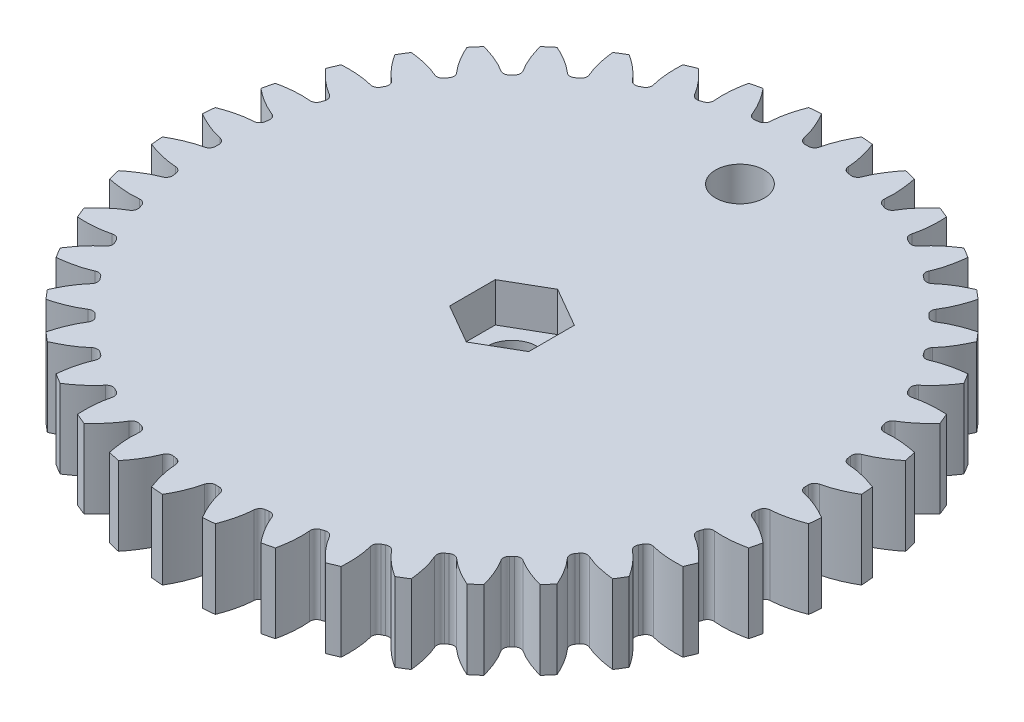
SolidWorks part; units mm, degrees
ref_plane "Front Plane" through (0, 0, 0) normal (0, 0, 1) x (1, 0, 0)
ref_plane "Top Plane" through (0, 0, 0) normal (0, 1, 0) x (1, 0, 0)
ref_plane "Right Plane" through (0, 0, 0) normal (1, 0, 0) x (0, 0, -1)
sketch "Sketch2" plane through (0, 0, 0) normal (0, 1, 0) x (1, 0, 0)
  circle A0 centre (0, 0) radius 53.34
  dimension "D1" = 106.68
extrude "Boss-Extrude1" add sketch "Sketch2" along normal blind 12.7
sketch "Sketch3" plane through (0, 0, 0) normal (0, -1, 0) x (-1, 0, 0)
  line L0 (0, 0) -> (47.7222, -1.163) construction
  line L1 (0, 0) -> (47.7222, 1.163) construction
  line L2 (47.7222, -1.163) -> (47.6109, -1.1603)
  line L3 (47.7222, 1.163) -> (47.6109, 1.1603)
  circle A0 centre (0, 0) radius 53.34
  circle A1 centre (0, 0) radius 50.8
  circle A2 centre (0, 0) radius 47.752
  circle A3 centre (0, 0) radius 47.625
  spline S0 degree 4 poles (47.7222, 1.163) (47.731, 1.1633) (47.7556, 1.1645) (47.802, 1.1678) (47.8777, 1.1747) (47.9741, 1.186) (48.0986, 1.2033) (48.2451, 1.2271) (48.4058, 1.257) (48.5805, 1.2934) (48.7546, 1.3332) (48.928, 1.3762) (49.1005, 1.4219) (49.3093, 1.4808) (49.5592, 1.5562) (49.8507, 1.6513) (50.1805, 1.7675) (50.5158, 1.8948) (50.845, 2.0273) (51.1768, 2.1695) (51.4972, 2.313) (51.8289, 2.4707) (52.1347, 2.6205) (52.4761, 2.7979) (52.7513, 2.9438) (53.113, 3.1463) (53.3263, 3.2689) (53.5754, 3.4159) (53.6857, 3.483) (53.7537, 3.5243) knots 0 0 0 0 0 0.005377 0.015084 0.028532 0.04661 0.064855 0.092111 0.119476 0.146842 0.174209 0.201575 0.228941 0.256307 0.307035 0.361767 0.4165 0.471232 0.525964 0.580697 0.635429 0.690161 0.744894 0.799626 0.854358 0.909091 0.954545 1 1 1 1 1 construction
  spline S1 degree 4 poles (47.7222, 1.163) (47.731, 1.1633) (47.7556, 1.1645) (47.802, 1.1678) (47.8777, 1.1747) (47.9741, 1.186) (48.0986, 1.2033) (48.2451, 1.2271) (48.4058, 1.257) (48.5805, 1.2934) (48.7546, 1.3332) (48.928, 1.3762) (49.1005, 1.4219) (49.3093, 1.4808) (49.5592, 1.5562) (49.8507, 1.6513) (50.1805, 1.7675) (50.5158, 1.8948) (50.845, 2.0273) (51.1768, 2.1695) (51.4972, 2.313) (51.8289, 2.4707) (52.1347, 2.6205) (52.4761, 2.7979) (52.7513, 2.9438) (53.0346, 3.1024) (53.1723, 3.1808) (53.2426, 3.2213) knots 0 0 0 0 0 0.005377 0.015084 0.028532 0.04661 0.064855 0.092111 0.119476 0.146842 0.174209 0.201575 0.228941 0.256307 0.307035 0.361767 0.4165 0.471232 0.525964 0.580697 0.635429 0.690161 0.744894 0.799626 0.854358 0.909091 0.909091 0.909091 0.909091 0.909091
  spline S2 degree 4 poles (47.7222, -1.163) (47.731, -1.1633) (47.7556, -1.1645) (47.802, -1.1678) (47.8777, -1.1747) (47.9741, -1.186) (48.0986, -1.2033) (48.2451, -1.2271) (48.4058, -1.257) (48.5805, -1.2934) (48.7546, -1.3332) (48.928, -1.3762) (49.1005, -1.4219) (49.3093, -1.4808) (49.5592, -1.5562) (49.8507, -1.6513) (50.1805, -1.7675) (50.5158, -1.8948) (50.845, -2.0273) (51.1768, -2.1695) (51.4972, -2.313) (51.8289, -2.4707) (52.1347, -2.6205) (52.4761, -2.7979) (52.7513, -2.9438) (53.113, -3.1463) (53.3263, -3.2689) (53.5754, -3.4159) (53.6857, -3.483) (53.7537, -3.5243) knots 0 0 0 0 0 0.005377 0.015084 0.028532 0.04661 0.064855 0.092111 0.119476 0.146842 0.174209 0.201575 0.228941 0.256307 0.307035 0.361767 0.4165 0.471232 0.525964 0.580697 0.635429 0.690161 0.744894 0.799626 0.854358 0.909091 0.954545 1 1 1 1 1 construction
  spline S3 degree 4 poles (47.7222, -1.163) (47.731, -1.1633) (47.7556, -1.1645) (47.802, -1.1678) (47.8777, -1.1747) (47.9741, -1.186) (48.0986, -1.2033) (48.2451, -1.2271) (48.4058, -1.257) (48.5805, -1.2934) (48.7546, -1.3332) (48.928, -1.3762) (49.1005, -1.4219) (49.3093, -1.4808) (49.5592, -1.5562) (49.8507, -1.6513) (50.1805, -1.7675) (50.5158, -1.8948) (50.845, -2.0273) (51.1768, -2.1695) (51.4972, -2.313) (51.8289, -2.4707) (52.1347, -2.6205) (52.4761, -2.7979) (52.7513, -2.9438) (53.0346, -3.1024) (53.1723, -3.1808) (53.2426, -3.2213) knots 0 0 0 0 0 0.005377 0.015084 0.028532 0.04661 0.064855 0.092111 0.119476 0.146842 0.174209 0.201575 0.228941 0.256307 0.307035 0.361767 0.4165 0.471232 0.525964 0.580697 0.635429 0.690161 0.744894 0.799626 0.854358 0.909091 0.909091 0.909091 0.909091 0.909091
  dimension "D1" = 106.68
  dimension "D2" = 101.6
  dimension "D3" = 95.504
  dimension "D4" = 95.25
extrude "Cut-Extrude1" cut sketch "Sketch3" against normal blind 12.7 contours A1 S3 A0 S1 | A2 S3 A1 S1 | L2 S3 A2 S1 L3 A3 region at (-47.6838, 0, 0) region at (-49.4115, 0, 0) region at (-52.1487, 0, 0)
fillet "Fillet2" radius 1.016 2 edges at (-47.6109, 6.35, -1.1603) (-47.6109, 6.35, 1.1603)
pattern_circular "CirPattern1" count 40 over 360 about axis through (0, 12.7, 0) along (0, 1, 0) of "Fillet2", "Cut-Extrude1"
sketch "Sketch4" plane through (0, 12.7, 0) normal (0, 1, 0) x (1, 0, 0)
  circle A0 centre (0, 0) radius 4.0957
  dimension "D1" = 8.1915
extrude "Cut-Extrude2" cut sketch "Sketch4" against normal through all
sketch "Sketch5" plane through (0, 12.7, 0) normal (0, 1, 0) x (1, 0, 0)
  line L1 (0, 7.3763) -> (-6.3881, 3.6882)
  line L2 (-6.3881, 3.6882) -> (-6.3881, -3.6882)
  line L3 (-6.3881, -3.6882) -> (0, -7.3763)
  line L4 (0, -7.3763) -> (6.3881, -3.6882)
  line L5 (6.3881, -3.6882) -> (6.3881, 3.6882)
  line L6 (6.3881, 3.6882) -> (0, 7.3763)
  circle A0 centre (0, 0) radius 6.3881 construction
  dimension "D1" = 12.7762
extrude "Cut-Extrude3" cut sketch "Sketch5" against normal blind 6.35
sketch "Sketch6" plane through (0, 12.7, 0) normal (0, 1, 0) x (1, 0, 0)
  line L0 (0, 0) -> (0, 36.83) construction
  circle A0 centre (0, 36.83) radius 3.937
  dimension "D2" = 7.874
  dimension "D1" = 36.83
extrude "Cut-Extrude4" cut sketch "Sketch6" against normal through all both and the other way through all
equation "\"DiametralPitch\"= 10"
equation "\"NumTeeth\"= 40"
equation "\"PressureAngle\"= 20deg"
equation "\"Addendum\"= 1 / \"DiametralPitch\""
equation "\"Dedendum\"= 1.25 / \"DiametralPitch\""
equation "\"WorkingDepth\"= 2 / \"DiametralPitch\""
equation "\"WholeDepth\"= 2.25 / \"DiametralPitch\""
equation "\"Clearance\"= 0.3 / \"DiametralPitch\""
equation "\"ToothThickness\"= 1.5708 / \"DiametralPitch\""
equation "\"CircularPitch\"= pi / \"DiametralPitch\""
equation "\"PitchCircle\"= \"NumTeeth\" / \"DiametralPitch\""
equation "\"OutsideDiameter\"= ( \"NumTeeth\" + 2 ) / \"DiametralPitch\""
equation "\"Fillet\"= \"Clearance\" * cos ( \"PressureAngle\" ) * tan ( ( 90 + \"PressureAngle\" ) / 2 )"
equation "\"AddendumCircle\"= \"PitchCircle\" + ( 2 * \"Addendum\" )"
equation "\"DedendumCircle\"= \"PitchCircle\" - ( 2 * \"Dedendum\" )"
equation "\"BaseCircle\"= \"PitchCircle\" * cos ( \"PressureAngle\" )"
equation "\"PitchAngle\"= 360deg / \"NumTeeth\""
equation "\"Alpha\"= sqr ( \"PitchCircle\" ^ 2 - \"BaseCircle\" ^ 2 ) / \"BaseCircle\" * 180 / PI - \"PressureAngle\""
equation "\"Beta\"= ( \"PitchAngle\" / 4 - \"Alpha\" )"
equation "\"Phi\"= sqr ( ( \"AddendumCircle\" / 2 ) ^ 2 - ( \"BaseCircle\" / 2 ) ^ 2 ) / ( \"BaseCircle\" / 2 )"
